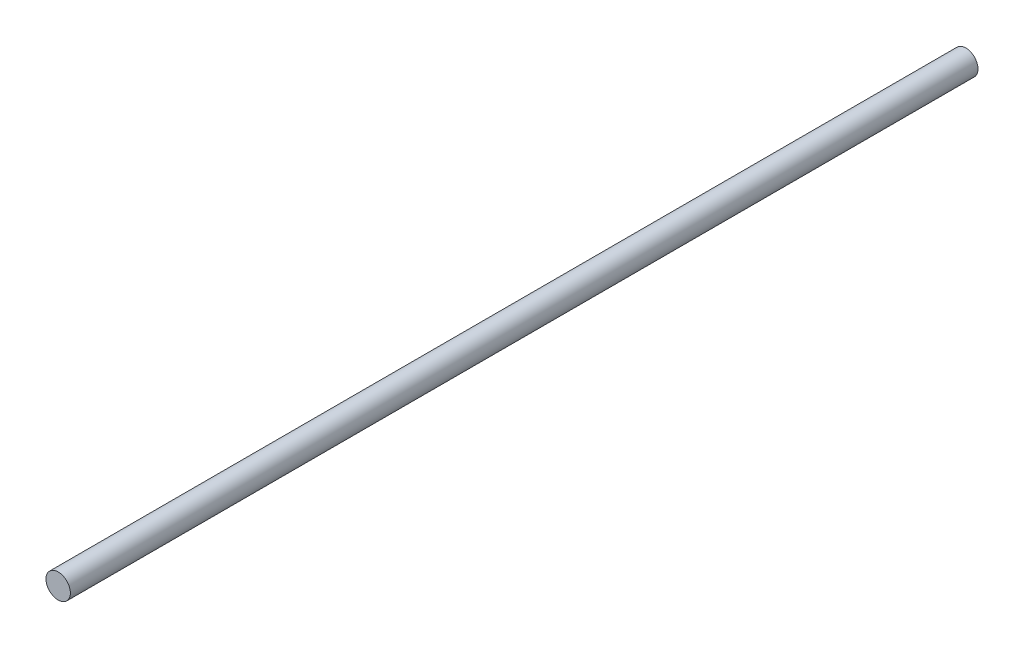
SolidWorks part; units mm, degrees
ref_plane "Front Plane" through (0, 0, 0) normal (0, 0, 1) x (1, 0, 0)
ref_plane "Top Plane" through (0, 0, 0) normal (0, 1, 0) x (1, 0, 0)
ref_plane "Right Plane" through (0, 0, 0) normal (1, 0, 0) x (0, 0, -1)
sketch "Sketch3" plane through (0, 0, 0) normal (0, 0, 1) x (1, 0, 0)
  circle A0 centre (0, 0) radius 25
  dimension "D1" = 50
extrude "Boss-Extrude1" add sketch "Sketch3" against normal blind 1861.1
